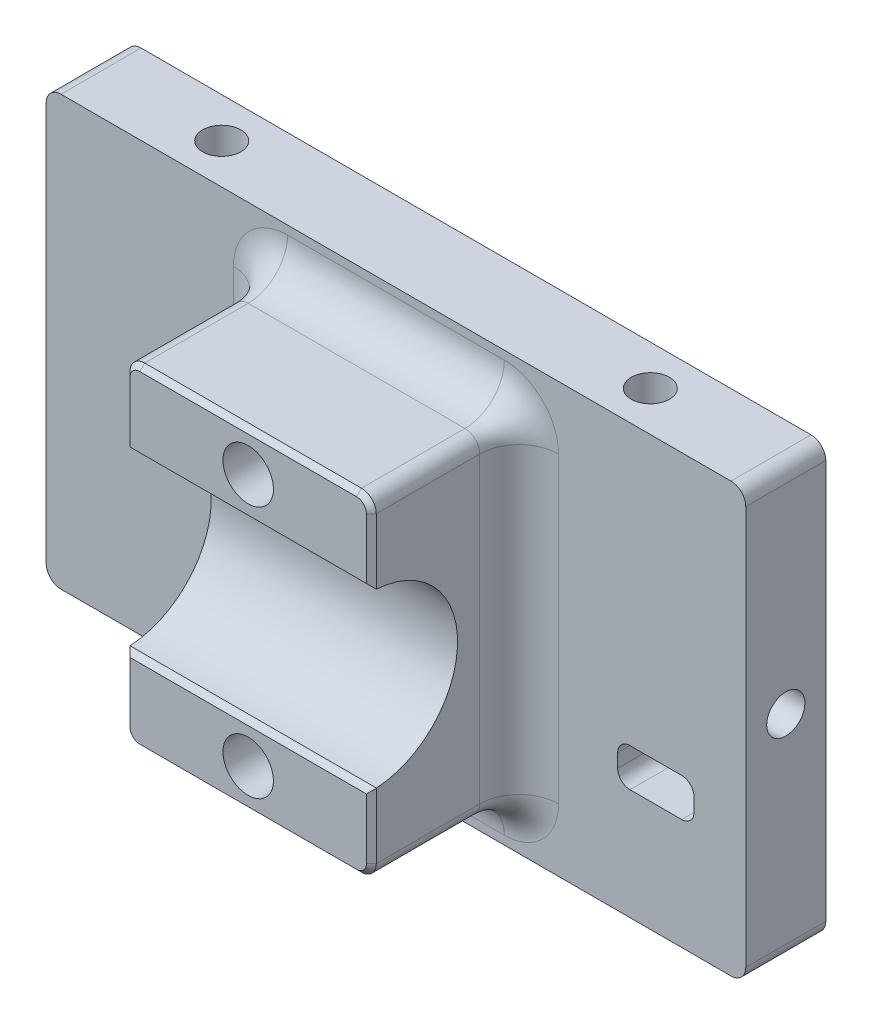
SolidWorks part; units mm, degrees
ref_plane "Plan de face" through (0, 0, 0) normal (0, 0, 1) x (1, 0, 0)
ref_plane "Plan de dessus" through (0, 0, 0) normal (0, 1, 0) x (1, 0, 0)
ref_plane "Plan de droite" through (0, 0, 0) normal (1, 0, 0) x (0, 0, -1)
sketch "Esquisse1" plane through (0, 0, 0) normal (0, 0, 1) x (1, 0, 0)
  line L1 (28.4, 17.4) -> (-28.4, 17.4)
  line L2 (28.4, 17.4) -> (28.4, -17.4)
  line L3 (28.4, -17.4) -> (-28.4, -17.4)
  line L4 (-28.4, 17.4) -> (-28.4, -17.4)
  line L5 (28.4, 17.4) -> (-28.4, -17.4) construction
  line L6 (28.4, -17.4) -> (-28.4, 17.4) construction
  point P0 (0, 0)
  dimension "D1" = 56.8
  dimension "D2" = 34.8
extrude "Base" add sketch "Esquisse1" along normal blind 6.5
sketch "Esquisse2" plane through (-28.4, 0, 0) normal (-1, 0, 0) x (0, 0, 1)
  line L0 (6.5, -17.4) -> (0, -17.4) construction
  circle A0 centre (3.25, 0) radius 1.55
  point P5 (3.25, -17.4)
  dimension "D1" = 3.1
sketch "Esquisse3" plane through (28.4, 0, 0) normal (1, 0, 0) x (0, 0, -1)
  circle A0 centre (-3.25, 0) radius 1.55
  circle A1 centre (-3.25, 0) radius 1.55 construction
extrude "Insert_M3_L" cut sketch "Esquisse2" against normal blind 3.2 contours A0
extrude "Insert_M3_R" cut sketch "Esquisse3" against normal blind 3.2
sketch "Esquisse4" plane through (0, 17.4, 0) normal (0, 1, 0) x (1, 0, 0)
  line L0 (-28.4, -6.5) -> (-28.4, 0) construction
  line L1 (28.4, -6.5) -> (28.4, 0) construction
  circle A0 centre (-17.4, -3.25) radius 1.55
  circle A1 centre (17.4, -3.25) radius 1.55
  point P9 (-28.4, -3.25)
  dimension "D3" = 3.1
  dimension "D1" = 11
  dimension "D2" = 11
sketch "Esquisse5" plane through (0, -17.4, -17) normal (0, 1, 0) x (1, 0, 0)
  circle A0 centre (-17.4, -20.25) radius 1.55
  circle A1 centre (17.4, -20.25) radius 1.55
  dimension "D3" = 3.1
extrude "Insert_M3_TOP" cut sketch "Esquisse4" against normal blind 3.2
extrude "Insert_M3_BOT" cut sketch "Esquisse5" along normal blind 3.2
sketch "Esquisse11" plane through (-25.2, 0, 0) normal (-1, 0, 0) x (0, 0, 1)
  circle A0 centre (3.25, 0) radius 1.1
  dimension "D1" = 2.2
extrude "Passage_Vis_L" cut sketch "Esquisse11" against normal blind 5
sketch "Esquisse12" plane through (25.2, 0, 0) normal (1, 0, 0) x (0, 0, -1)
  circle A0 centre (-3.25, 0) radius 1.1
  dimension "D1" = 2.2
extrude "Passage_Vis_R" cut sketch "Esquisse12" against normal blind 5
sketch "Esquisse10" plane through (0, 14.2, 0) normal (0, 1, 0) x (1, 0, 0)
  circle A0 centre (-17.4, -3.25) radius 1.1
  circle A1 centre (17.4, -3.25) radius 1.1
  dimension "D1" = 2.2
extrude "Passage_Vis_TOP" cut sketch "Esquisse10" against normal blind 5
sketch "Esquisse13" plane through (0, -14.2, 0) normal (0, -1, 0) x (1, 0, 0)
  circle A0 centre (-17.4, 3.25) radius 1.1
  circle A1 centre (17.4, 3.25) radius 1.1
  dimension "D1" = 2.2
extrude "Passage_Vis_BOT" cut sketch "Esquisse13" against normal blind 5
fillet "Congé1" radius 1.2 4 edges at (-28.4, -17.4, 3.25) (28.4, -17.4, 3.25) (28.4, 17.4, 3.25) (-28.4, 17.4, 3.25)
chamfer "Chanfrein1" [suppressed] distance 1 angle 45
sketch "Esquisse6" plane through (0, 0, 6.5) normal (0, 0, 1) x (1, 0, 0)
  line L1 (10, 13.5) -> (-10, 13.5)
  line L2 (10, 13.5) -> (10, -13.5)
  line L3 (10, -13.5) -> (-10, -13.5)
  line L4 (-10, 13.5) -> (-10, -13.5)
  line L5 (10, 13.5) -> (-10, -13.5) construction
  line L6 (10, -13.5) -> (-10, 13.5) construction
  point P0 (0, 0)
  dimension "D1" = 20
  dimension "D2" = 27
extrude "Support_Fixation" add sketch "Esquisse6" along normal blind 12
sketch "Esquisse7" plane through (-10, 0, 0) normal (-1, 0, 0) x (0, 0, 1)
  line L0 (18.5, 13.5) -> (18.5, -13.5) construction
  line L1 (18.5, 7) -> (18.5, -7)
  arc A0 (18.5, 7) -> (18.5, -7) centre (18.5, 0) ccw
  dimension "D1" = 7
extrude "Passage_Guidon" cut sketch "Esquisse7" against normal up to next
fillet "Congé_Vertical" radius 1.2 4 edges at (-10, 13.5, 12.5) (10, 13.5, 12.5) (10, -13.5, 12.5) (-10, -13.5, 12.5)
fillet "Congé_Base" radius 3.2 8 edges at (-9.6485, -13.1485, 6.5) (-10, 0, 6.5) (-9.6485, 13.1485, 6.5) (0, 13.5, 6.5) (9.6485, 13.1485, 6.5) (10, 0, 6.5) (9.6485, -13.1485, 6.5) (0, -13.5, 6.5)
sketch "Esquisse8" plane through (0, 0, 18.5) normal (0, 0, 1) x (1, 0, 0)
  line L1 (10, 7) -> (-10, 7) construction
  line L2 (55, 0) -> (-55, 0) construction
  line L3 (8.8, 13.5) -> (-8.8, 13.5) construction
  circle A0 centre (0, 10.25) radius 2.05
  circle A1 centre (0, -10.25) radius 2.05
  point P17 (0, 13.5)
  dimension "D1" = 4.1
  dimension "D2" = 3.25
extrude "Inserts_M3_Fixation" cut sketch "Esquisse8" against normal blind 4.2
chamfer "Chanfrein_Fixation" distance 0.4 angle 45 12 edges at (0, -7, 18.5) (0, 7, 18.5) (-10, -9.65, 18.5) (10, -9.65, 18.5) (-9.6485, -13.1485, 18.5) (9.6485, -13.1485, 18.5) (0, -13.5, 18.5) (10, 9.65, 18.5) (-10, 9.65, 18.5) (9.6485, 13.1485, 18.5) (-9.6485, 13.1485, 18.5) (0, 13.5, 18.5)
sketch "Esquisse9" plane through (0, 0, 14.3) normal (0, 0, 1) x (1, 0, 0)
  line L0 (55, 0) -> (-55, 0) construction
  circle A0 centre (0, 10.25) radius 1.6
  circle A1 centre (0, -10.25) radius 1.6
  dimension "D1" = 3.2
extrude "Passage_Vis_M3" cut sketch "Esquisse9" against normal blind 5
sketch "Esquisse14" plane through (0, 0, 6.5) normal (0, 0, 1) x (1, 0, 0)
  line L0 (-27.2, -17.4) -> (27.2, -17.4) construction
  line L1 (19, -5.3) -> (23.2, -5.3)
  line L2 (18, -6.3) -> (18, -7.4)
  line L3 (19, -8.4) -> (23.2, -8.4)
  line L4 (24.2, -6.3) -> (24.2, -7.4)
  line L5 (10, -12.3) -> (10, 12.3) construction
  arc A2 (23.2, -5.3) -> (24.2, -6.3) centre (23.2, -6.3) cw
  arc A3 (23.2, -8.4) -> (24.2, -7.4) centre (23.2, -7.4) ccw
  arc A4 (18, -7.4) -> (19, -8.4) centre (19, -7.4) ccw
  arc A5 (19, -5.3) -> (18, -6.3) centre (19, -6.3) ccw
  point P10 (24.2, -5.3)
  point P13 (24.2, -8.4)
  point P18 (18, -5.3)
  dimension "D5" = 1
  dimension "D1" = 6.2
  dimension "D2" = 3.1
  dimension "D3" = 9
  dimension "D4" = 8
extrude "Passe_Cable" cut sketch "Esquisse14" against normal blind 8 contours L4 L1 L2 L3 region at (21.1, -6.85, 6.5)
